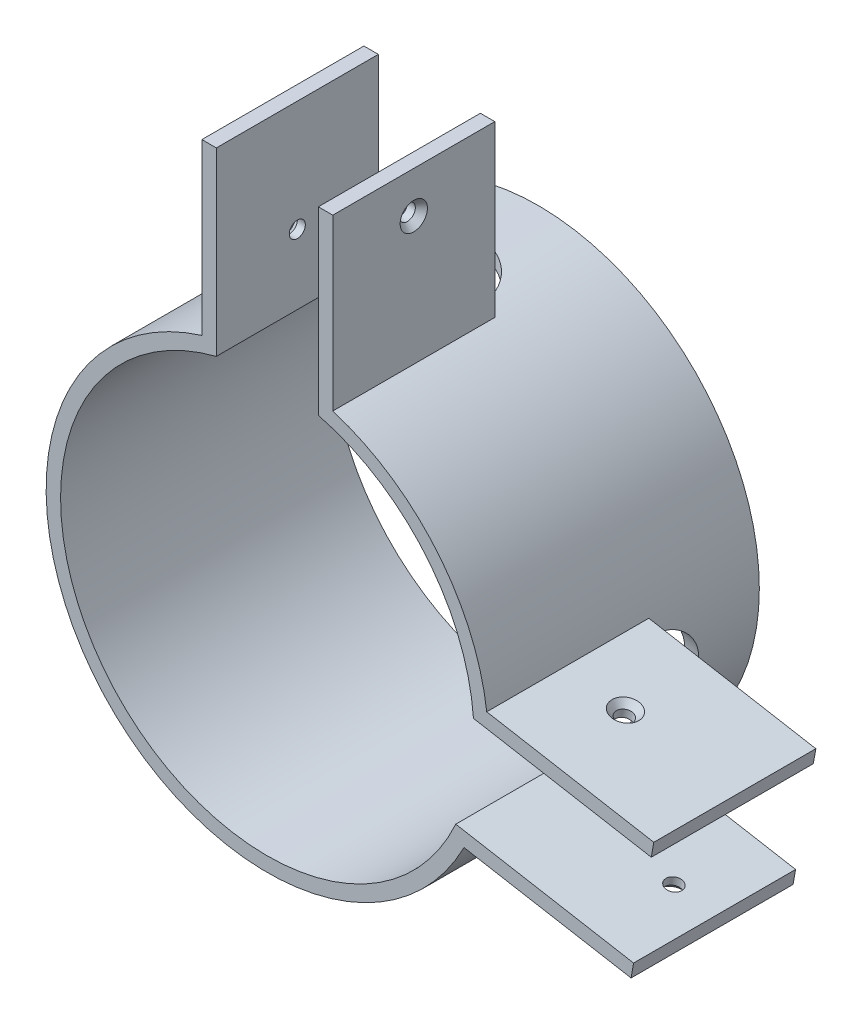
SolidWorks part; units mm, degrees
ref_plane "Plan de face" through (0, 0, 0) normal (0, 0, 1) x (1, 0, 0)
ref_plane "Plan de dessus" through (0, 0, 0) normal (0, 1, 0) x (1, 0, 0)
ref_plane "Plan de droite" through (0, 0, 0) normal (1, 0, 0) x (0, 0, -1)
sketch "Esquisse1" plane through (0, 0, 0) normal (0, 0, 1) x (1, 0, 0)
  line L0 (0, 0) -> (0, 24.5) construction
  line L1 (0, 0) -> (22.5521, -3.9765) construction
  circle A0 centre (0, 0) radius 22.9
  circle A1 centre (0, 0) radius 24.5
  dimension "D1" = 45.8
  dimension "D3" = 100
  dimension "D2" = 1.6
extrude "Boss.-Extru.1" add sketch "Esquisse1" along normal blind 30
sketch "Esquisse2" plane through (0, 0, 0) normal (0, 1, 0) x (1, 0, 0)
  line L1 (-24.5, -30) -> (24.5, -30) construction
  line L2 (-5.65, -30) -> (-5.65, -12.0501)
  line L3 (5.65, -12.0501) -> (5.65, -30)
  line L6 (-5.65, -30) -> (5.65, -30)
  arc A0 (-5.65, -12.0501) -> (5.65, -12.0501) centre (0, -12.0501) cw
  dimension "D1" = 11.3
extrude "Enlèv. mat.-Extru.1" cut sketch "Esquisse2" along normal through all
sketch "Esquisse3" plane through (-5.65, 0, 0) normal (1, 0, 0) x (0, 0, -1)
  line L0 (-12.0501, 22.1921) -> (-30, 22.1921)
  line L1 (-12.0501, 22.1921) -> (-12.0501, 42.1921)
  line L2 (-30, 22.1921) -> (-30, 42.1921)
  line L3 (-12.0501, 42.1921) -> (-30, 42.1921)
  dimension "D1" = 20
extrude "Boss.-Extru.2" add sketch "Esquisse3" against normal blind 1.6
sketch "Esquisse4" plane through (5.65, 0, 0) normal (-1, 0, 0) x (0, 0, 1)
  line L0 (30, 22.1921) -> (12.0501, 22.1921)
  line L1 (30, 22.1921) -> (30, 42.1921)
  line L2 (12.0501, 22.1921) -> (12.0501, 42.1921)
  line L3 (30, 42.1921) -> (12.0501, 42.1921)
  dimension "D1" = 20
extrude "Boss.-Extru.3" add sketch "Esquisse4" against normal blind 1.6
hole_wizard "Fraisage pour vis à tête fraisée bombée #01" positions "Esquisse5" profile "Esquisse6" countersink size "#0" standard "Ansi Inch" end condition up to next
sketch "Esquisse5" plane through (7.25, 0, 0) normal (1, 0, 0) x (0, 0, -1)
  point P0 (-21.0251, 37.6189)
sketch "Esquisse6" plane through (7.25, 37.6189, 21.0251) normal (0, 1, 0) x (0, 0, -1)
  line L0 (0, 0) -> (0, 1.6)
  line L1 (0, 1.6) -> (0.889, 1.6)
  line L2 (0.889, 1.6) -> (0.889, 0.7159)
  line L3 (0.889, 0.7159) -> (1.5113, 0)
  line L5 (1.5113, 0) -> (0, 0)
  line L6 (-0.889, 0.7159) -> (-1.5113, 0) construction
  line L11 (0, -6.35) -> (0, 107.95) construction
  dimension "Diamètre du perçage jusqu'au prochain" = 1.778
  dimension "Profondeur du perçage jusqu'au prochain" = 1.6
  dimension "Diamètre du fraisage entrant" = 3.0226
  dimension "Angle du fraisage entrant" = 82
hole_wizard "Fraisage pour vis à tête fraisée bombée #02" positions "Esquisse7" profile "Esquisse8" countersink size "#0" standard "Ansi Inch" end condition up to next
sketch "Esquisse7" plane through (-7.25, 0, 0) normal (-1, 0, 0) x (0, 0, 1)
  point P0 (21.0251, 29.8931)
sketch "Esquisse8" plane through (-7.25, 29.8931, 21.0251) normal (0, 1, 0) x (0, 0, 1)
  line L0 (0, 0) -> (0, 1.6)
  line L1 (0, 1.6) -> (0.889, 1.6)
  line L2 (0.889, 1.6) -> (0.889, 0.7159)
  line L3 (0.889, 0.7159) -> (1.5113, 0)
  line L5 (1.5113, 0) -> (0, 0)
  line L6 (-0.889, 0.7159) -> (-1.5113, 0) construction
  line L11 (0, -6.35) -> (0, 107.95) construction
  dimension "Diamètre du perçage jusqu'au prochain" = 1.778
  dimension "Profondeur du perçage jusqu'au prochain" = 1.6
  dimension "Diamètre du fraisage entrant" = 3.0226
  dimension "Angle du fraisage entrant" = 82
pattern_circular "Répétition circulaire1" count 2 over 100 about axis through (0, 0, 0) along (0, 0, 1) of "Enlèv. mat.-Extru.1", "Boss.-Extru.2", "Boss.-Extru.3", "Fraisage pour vis à tête fraisée bombée #01", "Fraisage pour vis à tête fraisée bombée #02" reverse direction yes
